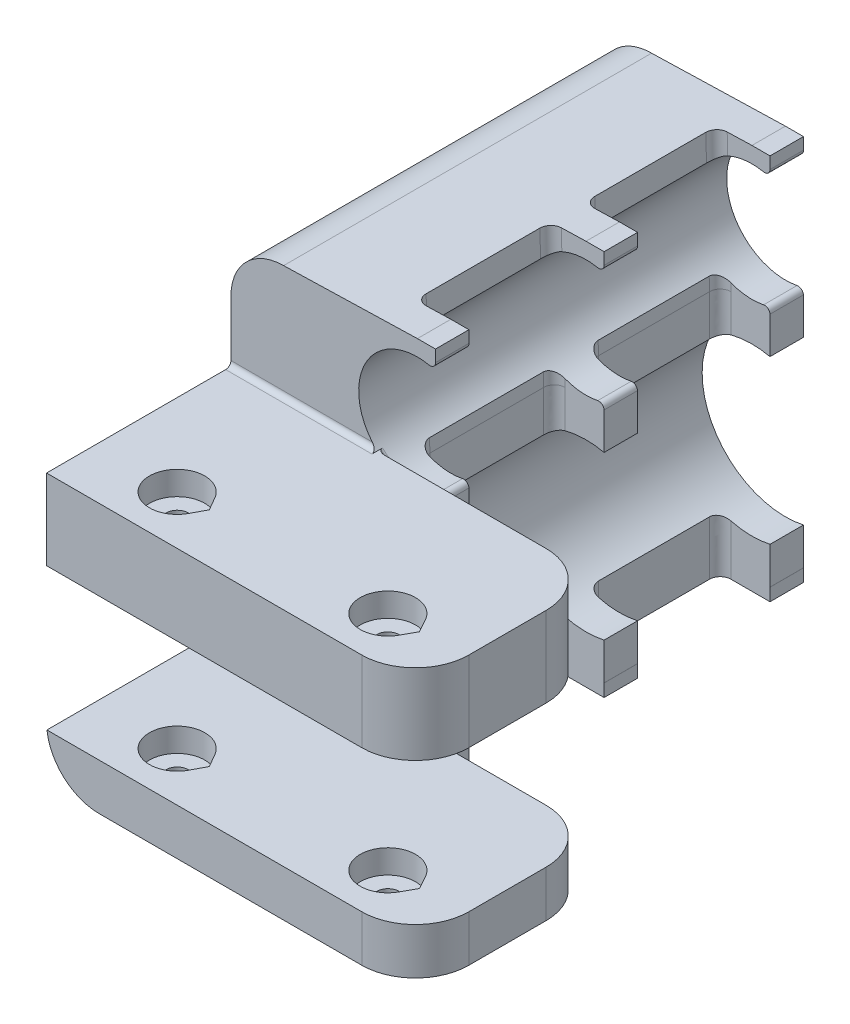
SolidWorks part; units mm, degrees
ref_plane "Front Plane" through (0, 0, 0) normal (0, 0, 1) x (1, 0, 0)
ref_plane "Top Plane" through (0, 0, 0) normal (0, 1, 0) x (1, 0, 0)
ref_plane "Right Plane" through (0, 0, 0) normal (1, 0, 0) x (0, 0, -1)
sketch "Sketch1" plane through (0, 0, 0) normal (0, 0, 1) x (1, 0, 0)
  line L0 (0, 0) -> (0, 13.2295) construction
  line L1 (3.429, -21.316) -> (3.429, -24.872)
  line L2 (0, -24.872) -> (-25.4, -24.872)
  line L3 (-25.4, 47.7241) -> (-25.4, -24.872)
  line L4 (3.429, 23.6544) -> (3.429, 21.316)
  line L5 (0, 48.4296) -> (-25.4, 47.7241)
  line L8 (0, 48.4296) -> (3.429, 48.4296)
  line L9 (3.429, 48.4296) -> (3.429, 44.8736)
  line L10 (3.429, -24.872) -> (0, -24.872)
  circle A0 centre (0, 0) radius 21.59 construction
  arc A1 (3.429, 21.316) -> (3.429, -21.316) centre (0, 0) ccw
  arc A2 (3.429, 44.8736) -> (3.429, 23.6544) centre (0, 34.264) ccw
  dimension "D1" = 22.3
  dimension "D2" = 3.556
  dimension "D3" = 3.556
  dimension "D4" = 3.429
  dimension "D5" = 25.4
extrude "Boss-Extrude1" add sketch "Sketch1" against normal blind 69.85
sketch "Sketch2" plane through (-1.3441, 48.3923, 0) normal (-0.0278, 0.9996, 0) x (0.9996, 0.0278, 0)
  line L0 (4.7723, 69.85) -> (4.7723, 0) construction
  line L1 (-5.3877, 63.5) -> (10.6572, 63.5)
  line L2 (-5.3877, 63.5) -> (-5.3877, 38.3544)
  line L3 (-5.3877, 38.3544) -> (10.6572, 38.3544)
  line L4 (10.6572, 63.5) -> (10.6572, 38.3544)
  line L5 (-5.3877, 32.0044) -> (10.6572, 32.0044)
  line L6 (-5.3877, 32.0044) -> (-5.3877, 6.35)
  line L7 (-5.3877, 6.35) -> (10.6572, 6.35)
  line L8 (10.6572, 32.0044) -> (10.6572, 6.35)
  line L9 (1.3446, 69.85) -> (-24.0652, 69.85) construction
  line L10 (1.3446, 0) -> (-24.0652, 0) construction
  dimension "D1" = 10.16
  dimension "D2" = 10.16
  dimension "D3" = 6.35
  dimension "D4" = 6.35
  dimension "D5" = 6.35
extrude "Cut-Extrude1" cut sketch "Sketch2" against normal through all and the other way blind 2.54
sketch "Sketch3" plane through (0, -24.872, 0) normal (0, -1, 0) x (1, 0, 0)
  line L0 (3.429, -32.0044) -> (-4.6989, -32.0044) construction
  line L1 (-4.6989, -6.35) -> (-14.8589, -6.35)
  line L3 (-7.6834, -32.0044) -> (-14.8589, -32.0044)
  line L4 (-14.8589, -6.35) -> (-14.8589, -32.0044)
  line L5 (-4.6989, -38.3544) -> (-14.8589, -38.3544)
  line L7 (-7.6834, -63.5) -> (-14.8589, -63.5)
  line L8 (-14.8589, -38.3544) -> (-14.8589, -63.5)
  line L9 (-4.6989, -6.35) -> (-4.3793, -6.35)
  line L11 (-7.6834, -32.0044) -> (-4.3793, -32.0044)
  line L12 (-4.3793, -6.35) -> (-4.3793, -32.0044)
  line L13 (3.429, -63.5) -> (-4.6989, -63.5) construction
  line L14 (-4.6989, -38.3544) -> (-2.4227, -38.3544)
  line L16 (-7.6834, -63.5) -> (-2.4227, -63.5)
  line L17 (-2.4227, -38.3544) -> (-2.4227, -63.5)
  dimension "D1" = 10.16
  dimension "D2" = 10.16
extrude "Cut-Extrude2" cut sketch "Sketch3" against normal blind 13.97
fillet "Fillet1" radius 1.016 12 edges at (3.429, 23.6544, -3.175) (3.429, -21.316, -3.175) (3.429, -21.316, -35.1794) (3.429, -21.316, -66.675) (3.429, 23.6544, -35.1794) (3.429, 23.6544, -66.675) (3.429, 44.8736, -3.175) (3.429, 44.8736, -35.1794) (3.429, 44.8736, -66.675) (3.429, 21.316, -66.675) (3.429, 21.316, -35.1794) (3.429, 21.316, -3.175)
fillet "Fillet2" radius 2.032 12 edges at (-6.6605, 45.75, -63.5) (-6.6605, 45.75, -32.0044) (-6.024, 22.834, -32.0044) (-6.024, 22.834, -63.5) (-14.8589, -20.2676, -63.5) (-14.8589, -20.2676, -38.3544) (-14.8589, -20.2676, -6.35) (-6.024, 22.834, -38.3544) (-6.6605, 45.75, -38.3544) (-6.6605, 45.75, -6.35) (-6.024, 22.834, -6.35) (-14.8589, -20.2676, -32.0044)
sketch "Sketch4" plane through (-25.4, 0, 0) normal (-1, 0, 0) x (0, 0, 1)
  line L0 (-69.85, 47.7241) -> (0, 47.7241) construction
  line L5 (0, 23.114) -> (0, 45.414) construction
  line L6 (0, 26.1341) -> (35, 26.1341)
  line L7 (0, 26.1341) -> (0, 10.8941)
  line L8 (0, 10.8941) -> (35, 10.8941)
  line L9 (35, 26.1341) -> (35, 10.8941)
  dimension "D1" = 15.24
  dimension "D2" = 21.59
  dimension "D3" = 35
extrude "Boss-Extrude2" add sketch "Sketch4" against normal blind 60
fillet "Fillet3" radius 10.16 2 edges at (34.6, 18.5141, 35) (34.6, 18.5141, 0)
sketch "Sketch5" plane through (0, 26.1341, 0) normal (0, 1, 0) x (1, 0, 0)
  line L0 (-25.4, -35) -> (-25.4, 0) construction
  line L2 (23.1, -25.7114) -> (21.5707, -24.211)
  line L3 (23.1, -25.7114) -> (21.5693, -27.2104)
  line L4 (-16.9, -25.602) -> (-18.4859, -24.1575)
  line L5 (-16.9, -25.602) -> (-18.3779, -27.1568)
  line L6 (-7.6307, 0) -> (-25.4, 0) construction
  arc A0 (21.5707, -24.211) -> (21.5693, -27.2104) centre (20.1, -25.71) ccw
  arc A1 (-18.4859, -24.1575) -> (-18.3779, -27.1568) centre (-19.9, -25.71) ccw
  point P0 (-19.9, -25.71)
  point P1 (20.1, -25.71)
  point P6 (23.1, -25.7114)
  point P11 (-16.9, -25.602)
  dimension "D5" = 4.2
  dimension "D1" = 40
  dimension "D2" = 5.5
  dimension "D3" = 25.71
  dimension "D4" = 25.71
  dimension "D6" = 3
  dimension "D7" = 3
extrude "Cut-Extrude3" cut sketch "Sketch5" against normal through all
sketch "Sketch6" plane through (0, 0, -69.85) normal (0, 0, -1) x (-1, 0, 0)
  line L0 (-3.429, -24.872) -> (-3.4285, -15.4235)
  line L1 (-3.4267, 22.4083) -> (25.4, 22.4083)
  line L2 (25.4, 47.7241) -> (25.4, -24.872) construction
  line L3 (25.4, 22.4083) -> (25.4, -24.872)
  line L4 (25.4, -24.872) -> (-3.429, -24.872)
  line L5 (-3.427, 15.4239) -> (-3.4267, 22.4083)
  arc A0 (-3.4285, -15.4235) -> (-3.427, 15.4239) centre (0, 0) ccw
  dimension "D1" = 31.6
extrude "Boss-Extrude3" add sketch "Sketch6" against normal blind 69.85
sketch "Sketch7" plane through (0, 22.4083, 0) normal (0, 1, 0) x (1, 0, 0)
  line L1 (3.4267, 32.0044) -> (-3.9794, 32.0044) construction
  line L2 (-6.0122, 29.9724) -> (-6.0122, 8.382) construction
  line L3 (-3.9794, 6.35) -> (3.4267, 6.35) construction
  line L5 (3.4267, 63.5) -> (-3.9794, 63.5) construction
  line L6 (-6.0122, 61.468) -> (-6.0122, 40.3864) construction
  line L7 (-3.9794, 38.3544) -> (3.4267, 38.3544) construction
  line L9 (3.4267, 32.0044) -> (-3.9794, 32.0044)
  line L10 (-6.0122, 29.9724) -> (-6.0122, 8.382)
  line L11 (-3.9794, 6.35) -> (3.4267, 6.35)
  line L13 (3.4267, 63.5) -> (-3.9794, 63.5)
  line L14 (-6.0122, 61.468) -> (-6.0122, 40.3864)
  line L15 (-3.9794, 38.3544) -> (3.4267, 38.3544)
  line L16 (3.4267, 63.5) -> (5.5294, 63.5)
  line L17 (5.5294, 63.5) -> (5.5294, 38.3544)
  line L18 (5.5294, 38.3544) -> (3.4267, 38.3544)
  line L19 (3.4267, 32.0044) -> (6.463, 32.0044)
  line L20 (6.463, 32.0044) -> (6.1335, 6.35)
  line L21 (6.1335, 6.35) -> (3.4267, 6.35)
  ellipse E0 centre (-3.9794, 29.9724) end of major axis (-6.0122, 29.9724) minor radius 2.032 (-3.9794, 32.0044) -> (-6.0122, 29.9724) ccw construction
  ellipse E1 centre (-3.9794, 8.382) end of major axis (-6.0122, 8.382) minor radius 2.032 (-6.0122, 8.382) -> (-3.9794, 6.35) ccw construction
  ellipse E2 centre (-3.9794, 61.468) end of major axis (-6.0122, 61.468) minor radius 2.032 (-3.9794, 63.5) -> (-6.0122, 61.468) ccw construction
  ellipse E3 centre (-3.9794, 40.3864) end of major axis (-6.0122, 40.3864) minor radius 2.032 (-6.0122, 40.3864) -> (-3.9794, 38.3544) ccw construction
  ellipse E4 centre (-3.9794, 29.9724) end of major axis (-6.0122, 29.9724) minor radius 2.032 (-3.9794, 32.0044) -> (-6.0122, 29.9724) ccw
  ellipse E5 centre (-3.9794, 8.382) end of major axis (-6.0122, 8.382) minor radius 2.032 (-6.0122, 8.382) -> (-3.9794, 6.35) ccw
  ellipse E6 centre (-3.9794, 61.468) end of major axis (-6.0122, 61.468) minor radius 2.032 (-3.9794, 63.5) -> (-6.0122, 61.468) ccw
  ellipse E7 centre (-3.9794, 40.3864) end of major axis (-6.0122, 40.3864) minor radius 2.032 (-6.0122, 40.3864) -> (-3.9794, 38.3544) ccw
extrude "Cut-Extrude4" cut sketch "Sketch7" against normal blind 69.85
sketch "Sketch9" plane through (0, 26.1341, 0) normal (0, 1, 0) x (1, 0, 0)
  line L0 (26.1, -25.7114) -> (24.6943, -23.1694)
  line L1 (26.1, -25.7114) -> (24.6932, -28.2527)
  line L2 (-13.9, -25.602) -> (-15.3535, -23.0848)
  line L3 (-13.9, -25.602) -> (-15.262, -28.1699)
  arc A0 (24.6943, -23.1694) -> (24.6932, -28.2527) centre (20.1, -25.71) ccw
  arc A1 (-15.3535, -23.0848) -> (-15.262, -28.1699) centre (-19.9, -25.71) ccw
  point P1 (0, 0)
  point P4 (27.2535, -25.3945)
  point P6 (26.1, -25.7114)
  point P7 (-13.9, -25.602)
  point P14 (0, 0)
  point P16 (-13.9, -25.5746)
  point P17 (0, 0)
  dimension "D1" = 10.5
  dimension "D2" = 6
  dimension "D3" = 6
extrude "Cut-Extrude5" cut sketch "Sketch9" against normal blind 4.5
sketch "Sketch10" plane through (0, 10.8941, 0) normal (0, -1, 0) x (1, 0, 0)
  line L0 (-13.9, 25.602) -> (-15.3535, 23.0848) construction
  line L1 (-15.262, 28.1699) -> (-13.9, 25.602) construction
  line L2 (24.6932, 28.2527) -> (26.1, 25.7114) construction
  line L3 (26.1, 25.7114) -> (24.6943, 23.1694) construction
  line L4 (-13.9, 25.602) -> (-15.3535, 23.0848)
  line L5 (-15.262, 28.1699) -> (-13.9, 25.602)
  line L6 (24.6932, 28.2527) -> (26.1, 25.7114)
  line L7 (26.1, 25.7114) -> (24.6943, 23.1694)
  arc A0 (-15.262, 28.1699) -> (-15.3535, 23.0848) centre (-19.9, 25.71) ccw construction
  arc A1 (24.6932, 28.2527) -> (24.6943, 23.1694) centre (20.1, 25.71) ccw construction
  arc A2 (-15.262, 28.1699) -> (-15.3535, 23.0848) centre (-19.9, 25.71) ccw
  arc A3 (24.6932, 28.2527) -> (24.6943, 23.1694) centre (20.1, 25.71) ccw
extrude "Cut-Extrude6" cut sketch "Sketch10" against normal blind 4.5
sketch "Sketch11" plane through (0, -24.872, 0) normal (0, -1, 0) x (1, 0, 0)
  line L1 (-18.3779, 27.1568) -> (-16.9, 25.602) construction
  line L2 (-16.9, 25.602) -> (-18.4859, 24.1575) construction
  line L3 (23.1, 25.7114) -> (21.5707, 24.211) construction
  line L4 (21.5693, 27.2104) -> (23.1, 25.7114) construction
  line L5 (34.6, 10.16) -> (34.6, 24.84)
  line L6 (24.44, 35) -> (-25.4, 35)
  line L7 (-25.4, 35) -> (-25.4, 0)
  line L8 (-25.4, 0) -> (-11.4437, 0)
  line L9 (-11.4437, 0) -> (24.44, 0)
  line L10 (34.6, 10.16) -> (34.6, 24.84)
  line L11 (24.44, 35) -> (-25.4, 35)
  line L12 (-25.4, 35) -> (-25.4, 0)
  line L13 (-25.4, 0) -> (-11.4437, 0)
  line L14 (-11.4437, 0) -> (24.44, 0)
  line L15 (-18.3779, 27.1568) -> (-16.9, 25.602)
  line L16 (-16.9, 25.602) -> (-18.4859, 24.1575)
  line L17 (23.1, 25.7114) -> (21.5707, 24.211)
  line L18 (21.5693, 27.2104) -> (23.1, 25.7114)
  arc A0 (-18.3779, 27.1568) -> (-18.4859, 24.1575) centre (-19.9, 25.71) ccw construction
  arc A1 (21.5693, 27.2104) -> (21.5707, 24.211) centre (20.1, 25.71) ccw construction
  arc A2 (34.6, 24.84) -> (24.44, 35) centre (24.44, 24.84) ccw
  arc A3 (24.44, 0) -> (34.6, 10.16) centre (24.44, 10.16) ccw
  arc A4 (34.6, 24.84) -> (24.44, 35) centre (24.44, 24.84) ccw
  arc A5 (24.44, 0) -> (34.6, 10.16) centre (24.44, 10.16) ccw
  arc A6 (-18.3779, 27.1568) -> (-18.4859, 24.1575) centre (-19.9, 25.71) ccw
  arc A7 (21.5693, 27.2104) -> (21.5707, 24.211) centre (20.1, 25.71) ccw
  dimension "D1" = 0
extrude "Boss-Extrude4" add sketch "Sketch11" against normal blind 8.8
sketch "Sketch12" plane through (0, -16.072, 0) normal (0, 1, 0) x (1, 0, 0)
  line L0 (-15.262, -28.1699) -> (-13.9, -25.602) construction
  line L1 (-13.9, -25.602) -> (-15.3535, -23.0848) construction
  line L2 (26.1, -25.7114) -> (24.6943, -23.1694) construction
  line L3 (24.6932, -28.2527) -> (26.1, -25.7114) construction
  line L4 (-15.262, -28.1699) -> (-13.9, -25.602)
  line L5 (-13.9, -25.602) -> (-15.3535, -23.0848)
  line L6 (26.1, -25.7114) -> (24.6943, -23.1694)
  line L7 (24.6932, -28.2527) -> (26.1, -25.7114)
  arc A0 (-15.3535, -23.0848) -> (-15.262, -28.1699) centre (-19.9, -25.71) ccw construction
  arc A1 (24.6943, -23.1694) -> (24.6932, -28.2527) centre (20.1, -25.71) ccw construction
  arc A2 (-15.3535, -23.0848) -> (-15.262, -28.1699) centre (-19.9, -25.71) ccw
  arc A3 (24.6943, -23.1694) -> (24.6932, -28.2527) centre (20.1, -25.71) ccw
extrude "Cut-Extrude7" cut sketch "Sketch12" against normal blind 4.5
sketch "Sketch13" plane through (0, 0, -69.85) normal (0, 0, -1) x (-1, 0, 0)
  line L1 (25.4, 47.7241) -> (35.4, 47.7241)
  line L2 (25.4, 47.7241) -> (25.4, -24.872)
  line L3 (25.4, -24.872) -> (35.4, -24.872)
  line L4 (35.4, 47.7241) -> (35.4, -24.872)
  dimension "D1" = 10
extrude "Boss-Extrude5" add sketch "Sketch13" against normal blind 69.85
sketch "Sketch14" plane through (-35.4, 0, 0) normal (-1, 0, 0) x (0, 0, 1)
  line L0 (35, -16.072) -> (0, -16.072) construction
  line L1 (0, -16.072) -> (0, -24.872) construction
  line L2 (0, -24.872) -> (35, -24.872) construction
  line L3 (35, -24.872) -> (35, -16.072) construction
  line L4 (35, 26.1341) -> (0, 26.1341) construction
  line L5 (0, 26.1341) -> (0, 10.8941) construction
  line L6 (0, 10.8941) -> (35, 10.8941) construction
  line L7 (35, 10.8941) -> (35, 26.1341) construction
  line L8 (35, -16.072) -> (0, -16.072)
  line L9 (0, -16.072) -> (0, -24.872)
  line L10 (0, -24.872) -> (35, -24.872)
  line L11 (35, -24.872) -> (35, -16.072)
  line L12 (35, 26.1341) -> (0, 26.1341)
  line L13 (0, 26.1341) -> (0, 10.8941)
  line L14 (0, 10.8941) -> (35, 10.8941)
  line L15 (35, 10.8941) -> (35, 26.1341)
extrude "Boss-Extrude6" add sketch "Sketch14" against normal blind 10
fillet "Fillet4" radius 10 2 edges at (-35.4, -24.872, -17.425) (-35.4, 47.7241, -34.925)
fillet "Fillet6" radius 1 3 edges at (-23.4218, 10.8941, 0) (-15.9496, -16.072, 0) (-21.5154, 26.1341, 0)
fillet "Fillet7" radius 1 4 edges at (3.0293, 23.1474, 0) (3.4287, -19.2667, 0) (-4.6039, 15.1144, 0) (-3.0496, 23.5392, 0)
fillet "Fillet8" radius 1 1 edges at (3.4268, 19.2401, 0)
